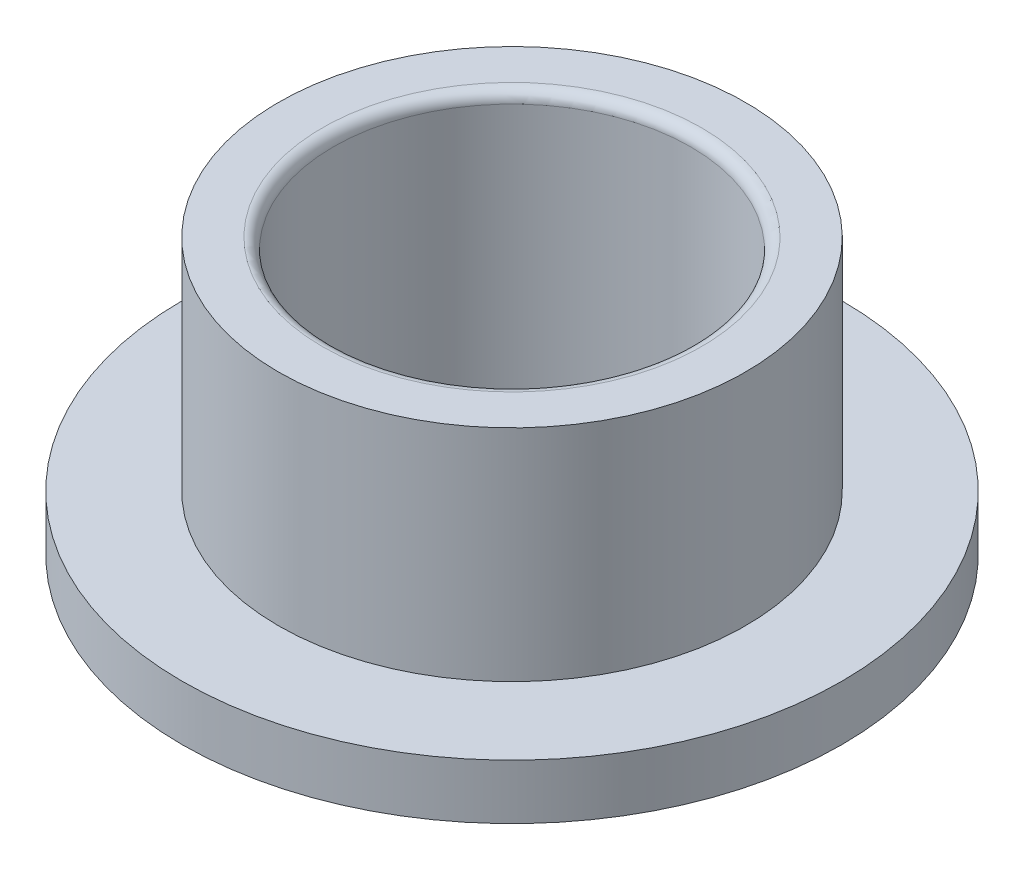
SolidWorks part; units mm, degrees
ref_plane "Front Plane" through (0, 0, 0) normal (0, 0, 1) x (1, 0, 0)
ref_plane "Top Plane" through (0, 0, 0) normal (0, 1, 0) x (1, 0, 0)
ref_plane "Right Plane" through (0, 0, 0) normal (1, 0, 0) x (0, 0, -1)
sketch "Sketch1" plane through (0, 0, 0) normal (0, 1, 0) x (1, 0, 0)
  circle A0 centre (0, 0) radius 16.25
  circle A1 centre (0, 0) radius 21.25
  dimension "D1" = 32.5
  dimension "D2" = 5
extrude "Boss-Extrude1" add sketch "Sketch1" along normal blind 20
fillet "Fillet1" radius 1 1 edges at (0, 20, 16.25)
sketch "Sketch2" plane through (0, 0, 0) normal (0, -1, 0) x (1, 0, 0)
  circle A0 centre (0, 0) radius 16.25 construction
  circle A1 centre (0, 0) radius 16.25
  circle A2 centre (0, 0) radius 30
  dimension "D1" = 60
extrude "Boss-Extrude2" add sketch "Sketch2" along normal blind 5
fillet "Fillet2" radius 1 1 edges at (0, -5, -16.25)
